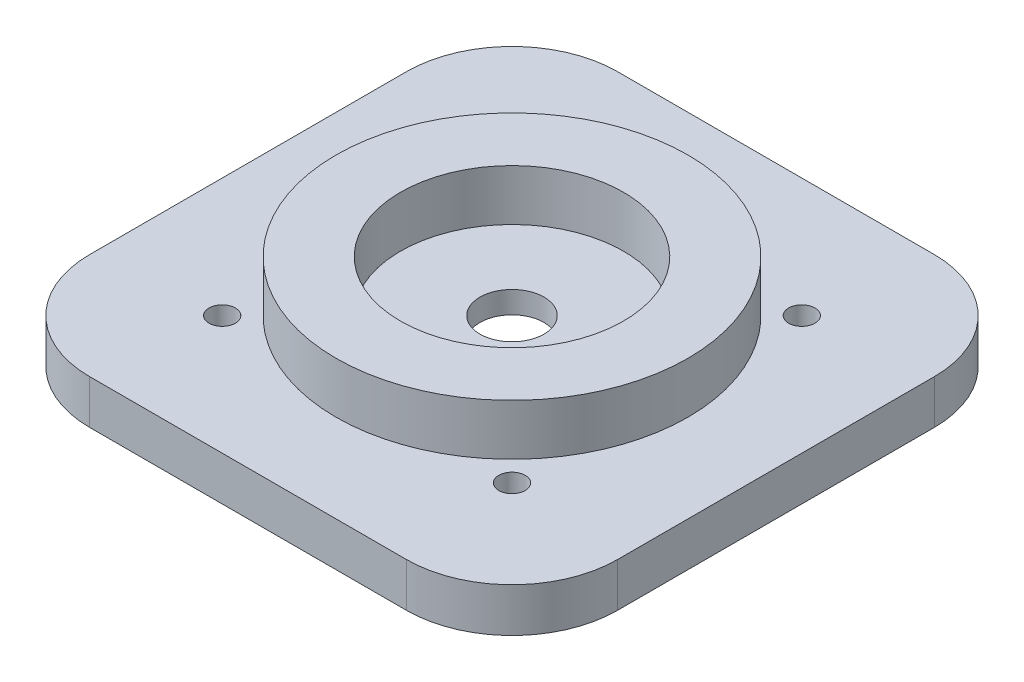
SolidWorks part; units mm, degrees
material "ABS PC"
ref_plane "Front Plane" through (0, 0, 0) normal (0, 0, 1) x (1, 0, 0)
ref_plane "Top Plane" through (0, 0, 0) normal (0, 1, 0) x (1, 0, 0)
ref_plane "Right Plane" through (0, 0, 0) normal (1, 0, 0) x (0, 0, -1)
sketch "Sketch1" plane through (0, 0, 0) normal (0, 1, 0) x (1, 0, 0)
  line L0 (0, 50.8) -> (4.4901, 46.3099)
  line L1 (0, 0) -> (50.8, 0)
  line L2 (0, 0) -> (0, 50.8)
  line L3 (0, 50.8) -> (50.8, 50.8)
  line L4 (50.8, 0) -> (50.8, 50.8)
  line L5 (0, 25.4) -> (50.8, 25.4) construction
  line L6 (25.4, 50.8) -> (25.4, 0) construction
  circle A0 centre (4.4901, 46.3099) radius 1.905
  circle A1 centre (4.4901, 4.4901) radius 1.905
  circle A2 centre (46.3099, 4.4901) radius 1.905
  circle A3 centre (46.3099, 46.3099) radius 1.905
  circle A28 centre (25.4, 25.4) radius 4.625
  dimension "D1" = 3.81
  dimension "D5" = 9.25
  dimension "D2" = 50.8
  dimension "D3" = 50.8
  dimension "D4" = 6.35
extrude "Boss-Extrude1" add sketch "Sketch1" along normal blind 6.35 contours A0 L2 L1 L4 L3 A1 A2 A3 region at (25.4, 0, -50.0816)
sketch "Sketch2" plane through (0, 0, 0) normal (0, 1, 0) x (1, 0, 0)
  line L0 (4.4901, 44.2975) -> (4.4901, 6.5025)
  line L1 (6.5025, 4.4901) -> (44.2975, 4.4901)
  line L2 (46.3099, 44.2975) -> (46.3099, 6.5025)
  line L3 (44.2975, 46.3099) -> (6.5025, 46.3099)
  circle A0 centre (4.4901, 46.3099) radius 1.905
  circle A1 centre (4.4901, 46.3099) radius 2.0124
  circle A2 centre (46.3099, 46.3099) radius 1.905
  circle A3 centre (46.3099, 46.3099) radius 2.0124
  circle A4 centre (46.3099, 4.4901) radius 1.905
  circle A5 centre (46.3099, 4.4901) radius 2.0124
  circle A6 centre (4.4901, 4.4901) radius 1.905
  circle A7 centre (4.4901, 4.4901) radius 2.0124
extrude "Cut-Extrude1" [suppressed] cut sketch "Sketch2" along normal blind 1.5875 from surface contours A7 L1 A5 L2 A3 L3 A1 L0
sketch "Sketch3" plane through (0, 0, 0) normal (0, 1, 0) x (1, 0, 0)
  line L0 (3.2513, 44.2975) -> (3.2513, 6.5025)
  line L1 (6.5025, 3.2513) -> (44.2975, 3.2513)
  line L2 (47.5487, 44.2975) -> (47.5487, 6.5025)
  line L3 (44.2975, 47.5487) -> (6.5025, 47.5487)
  circle A0 centre (3.2513, 47.5487) radius 1.905
  circle A1 centre (3.2513, 47.5487) radius 3.2513
  circle A2 centre (47.5487, 47.5487) radius 1.905
  circle A3 centre (47.5487, 47.5487) radius 3.2513
  circle A4 centre (47.5487, 3.2513) radius 1.905
  circle A5 centre (47.5487, 3.2513) radius 3.2513
  circle A6 centre (3.2513, 3.2513) radius 1.905
  circle A7 centre (3.2513, 3.2513) radius 3.2513
extrude "Cut-Extrude2" [suppressed] cut sketch "Sketch3" against normal blind 1.5875 from surface contours A7 L1 A5 L2 A3 L3 A1 L0
fillet "Fillet1" radius 2.54 4 edges at (50.8, 3.175, -50.8) (50.8, 3.175, 0) (0, 3.175, 0) (0, 3.175, -50.8)
sketch "Sketch4" plane through (0, 0, 0) normal (0, -1, 0) x (1, 0, 0)
  line L4 (10.2051, -4.4901) -> (40.5949, -4.4901)
  line L5 (46.3099, -10.2051) -> (46.3099, -40.5949)
  line L6 (40.5949, -46.3099) -> (10.2051, -46.3099)
  line L7 (4.4901, -40.5949) -> (4.4901, -10.2051)
  arc A4 (4.4901, -10.2051) -> (10.2051, -4.4901) centre (4.4901, -4.4901) ccw
  arc A5 (40.5949, -4.4901) -> (46.3099, -10.2051) centre (46.3099, -4.4901) ccw
  arc A6 (46.3099, -40.5949) -> (40.5949, -46.3099) centre (46.3099, -46.3099) ccw
  arc A7 (10.2051, -46.3099) -> (4.4901, -40.5949) centre (4.4901, -46.3099) ccw
  circle A8 centre (4.4901, -4.4901) radius 1.905
  dimension "D1" = 11.43
extrude "Cut-Extrude3" cut sketch "Sketch4" against normal blind 3.175
sketch "Sketch5" plane through (0, 6.35, 0) normal (0, 1, 0) x (1, 0, 0)
  line L8 (63.5, 2.54) -> (63.5, 48.26)
  line L9 (48.26, 63.5) -> (2.54, 63.5)
  line L10 (-12.7, 48.26) -> (-12.7, 2.54)
  line L11 (2.54, -12.7) -> (48.26, -12.7)
  line L12 (63.5, 2.54) -> (63.5, 48.26)
  line L13 (48.26, 63.5) -> (2.54, 63.5)
  line L14 (-12.7, 48.26) -> (-12.7, 2.54)
  line L15 (2.54, -12.7) -> (48.26, -12.7)
  line L16 (50.8, 2.54) -> (50.8, 48.26)
  line L17 (48.26, 50.8) -> (2.54, 50.8)
  line L18 (0, 48.26) -> (0, 2.54)
  line L19 (2.54, 0) -> (48.26, 0)
  line L20 (50.8, 2.54) -> (50.8, 48.26)
  line L21 (48.26, 50.8) -> (2.54, 50.8)
  line L22 (0, 48.26) -> (0, 2.54)
  line L23 (2.54, 0) -> (48.26, 0)
  arc A8 (63.5, 48.26) -> (48.26, 63.5) centre (48.26, 48.26) ccw
  arc A9 (2.54, 63.5) -> (-12.7, 48.26) centre (2.54, 48.26) ccw
  arc A10 (-12.7, 2.54) -> (2.54, -12.7) centre (2.54, 2.54) ccw
  arc A11 (48.26, -12.7) -> (63.5, 2.54) centre (48.26, 2.54) ccw
  arc A12 (63.5, 48.26) -> (48.26, 63.5) centre (48.26, 48.26) ccw
  arc A13 (2.54, 63.5) -> (-12.7, 48.26) centre (2.54, 48.26) ccw
  arc A14 (-12.7, 2.54) -> (2.54, -12.7) centre (2.54, 2.54) ccw
  arc A15 (48.26, -12.7) -> (63.5, 2.54) centre (48.26, 2.54) ccw
  arc A16 (50.8, 48.26) -> (48.26, 50.8) centre (48.26, 48.26) ccw
  arc A17 (2.54, 50.8) -> (0, 48.26) centre (2.54, 48.26) ccw
  arc A18 (0, 2.54) -> (2.54, 0) centre (2.54, 2.54) ccw
  arc A19 (48.26, 0) -> (50.8, 2.54) centre (48.26, 2.54) ccw
  arc A20 (50.8, 48.26) -> (48.26, 50.8) centre (48.26, 48.26) ccw
  arc A21 (2.54, 50.8) -> (0, 48.26) centre (2.54, 48.26) ccw
  arc A22 (0, 2.54) -> (2.54, 0) centre (2.54, 2.54) ccw
  arc A23 (48.26, 0) -> (50.8, 2.54) centre (48.26, 2.54) ccw
  dimension "D1" = 12.7
  dimension "D2" = 0
extrude "Boss-Extrude2" add sketch "Sketch5" against normal up to surface (6.35 mm away) up to face at (25.4, 0, -25.4)
sketch "Sketch6" plane through (0, 6.35, 0) normal (0, 1, 0) x (1, 0, 0)
  circle A0 centre (25.4, 25.4) radius 16.1
  circle A1 centre (25.4, 25.4) radius 25.4
  dimension "D1" = 50.8
  dimension "D2" = 32.2
extrude "Boss-Extrude3" add sketch "Sketch6" along normal blind 7.366
